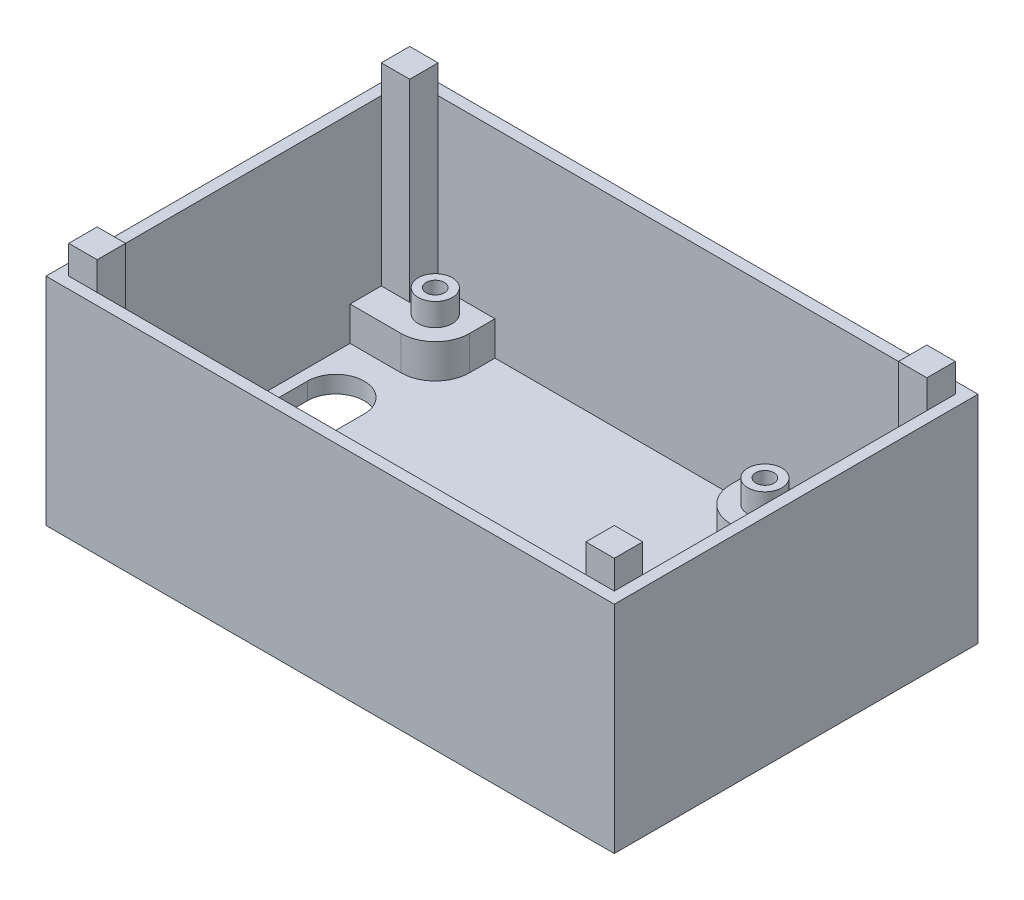
SolidWorks part; units mm, degrees
material "ABS"
ref_plane "Front Plane" through (0, 0, 0) normal (0, 0, 1) x (1, 0, 0)
ref_plane "Top Plane" through (0, 0, 0) normal (0, 1, 0) x (1, 0, 0)
ref_plane "Right Plane" through (0, 0, 0) normal (1, 0, 0) x (0, 0, -1)
sketch "Sketch1" plane through (0, 0, 0) normal (0, 1, 0) x (1, 0, 0)
  line L0 (-55, 0) -> (55, 0) construction
  line L1 (-50, 32) -> (50, 32)
  line L2 (-50, 32) -> (-50, -32)
  line L3 (-50, -32) -> (50, -32)
  line L4 (50, 32) -> (50, -32)
  line L5 (0, -55) -> (0, 55) construction
  dimension "D1" = 64
  dimension "D2" = 32
  dimension "D3" = 100
  dimension "D4" = 50
extrude "Boss-Extrude1" add sketch "Sketch1" along normal blind 3
sketch "Sketch2" plane through (0, 3, 0) normal (0, 1, 0) x (1, 0, 0)
  line L0 (50, 32) -> (-50, 32) construction
  line L1 (-48, -30) -> (48, -30)
  line L2 (-48, -30) -> (-48, 30)
  line L3 (-48, 30) -> (48, 30)
  line L4 (48, -30) -> (48, 30)
  line L5 (-48, -30) -> (48, 30) construction
  line L6 (-48, 30) -> (48, -30) construction
  line L7 (-50, 32) -> (-50, -32) construction
  line L9 (-50, 32) -> (50, 32)
  line L10 (-50, 32) -> (-50, -32)
  line L11 (-50, -32) -> (50, -32)
  line L12 (50, 32) -> (50, -32)
  point P0 (0, 0)
  dimension "D1" = 2
  dimension "D2" = 2
extrude "Boss-Extrude2" add sketch "Sketch2" along normal blind 35
sketch "Sketch6" plane through (0, 3, 0) normal (0, 1, 0) x (1, 0, 0)
  line L0 (-42.5, 30) -> (-42.5, -30) construction
  line L5 (-48, -30) -> (48, -30) construction
  line L6 (42.5, 30) -> (42.5, -30) construction
  line L7 (48, 30) -> (-48, 30) construction
  line L8 (-48, 30) -> (-48, -30) construction
  line L9 (48, -30) -> (48, 30) construction
  line L10 (-39, 28.5) -> (-39, -30) construction
  line L11 (-48, -23.5) -> (42.5, -23.5) construction
  line L12 (-48, 25.5) -> (42.5, 25.5) construction
  line L13 (-48, -30) -> (48, -30) construction
  line L14 (19, 27.1) -> (19, -30) construction
  line L16 (35.5962, 0) -> (7.276, 0) construction
  line L25 (-1.65, 0) -> (1.65, 0) construction
  circle A0 centre (-39, 25.5) radius 1.6
  circle A1 centre (19, 25.5) radius 1.6
  circle A2 centre (19, -23.5) radius 1.6
  circle A3 centre (-39, -23.5) radius 1.6
  circle A4 centre (-39, 25.5) radius 3
  circle A5 centre (19, 25.5) radius 3
  circle A6 centre (-39, -23.5) radius 3
  circle A7 centre (19, -23.5) radius 3
  dimension "D8" = 3.2
  dimension "D11" = 6
  dimension "D12" = 6
  dimension "D2" = 5.5
  dimension "D3" = 5.5
  dimension "D4" = 4.5
  dimension "D5" = 3.5
  dimension "D6" = 6.5
  dimension "D7" = 58
  dimension "D13" = 2
  dimension "D9" = 2
  dimension "D10" = 2
extrude "Boss-Extrude3" add sketch "Sketch6" along normal blind 10
sketch "Sketch7" plane through (0, 3, 0) normal (0, 1, 0) x (1, 0, 0)
  circle A0 centre (-39, 25.5) radius 1.5
  circle A1 centre (19, 25.5) radius 1.5
  circle A2 centre (19, -23.5) radius 1.5
  circle A3 centre (-39, -23.5) radius 1.5
  dimension "D3" = 3
  dimension "D1" = 2
  dimension "D2" = 2
extrude "Cut-Extrude2" cut sketch "Sketch7" against normal through all
sketch "Sketch10" plane through (0, 13, 0) normal (0, 1, 0) x (1, 0, 0)
  line L0 (-33, 25.5) -> (-33, 30)
  line L1 (48, 30) -> (-48, 30) construction
  line L2 (-39, 19.5) -> (-48, 19.5)
  line L3 (-48, 30) -> (-48, -30) construction
  line L4 (25, 25.5) -> (25, 30)
  line L5 (48, 30) -> (-48, 30) construction
  line L6 (13, 25.5) -> (13, 30)
  line L7 (25, -23.5) -> (25, -30)
  line L8 (-48, -30) -> (48, -30) construction
  line L9 (25, -30) -> (13, -30)
  line L10 (-48, -30) -> (48, -30) construction
  line L11 (13, -30) -> (13, -23.5)
  line L12 (25, 30) -> (13, 30)
  line L13 (-33, 30) -> (-48, 30)
  line L14 (-48, 30) -> (-48, 19.5)
  line L15 (-33, -23.5) -> (-33, -30)
  line L16 (-33, -30) -> (-48, -30)
  line L17 (-48, -30) -> (-48, -17.5)
  line L18 (-48, 30) -> (-48, -30) construction
  line L19 (-48, -17.5) -> (-39, -17.5)
  line L21 (48, 30) -> (38, 30)
  line L22 (48, 30) -> (48, 19.5)
  line L23 (48, 19.5) -> (38, 19.5)
  line L24 (38, 30) -> (38, 19.5)
  line L25 (48, -30) -> (38, -30)
  line L26 (48, -30) -> (48, -20)
  line L27 (48, -20) -> (38, -20)
  line L28 (38, -30) -> (38, -20)
  circle A0 centre (-39, 25.5) radius 3
  arc A1 (-39, 19.5) -> (-33, 25.5) centre (-39, 25.5) ccw
  arc A2 (13, 25.5) -> (25, 25.5) centre (19, 25.5) ccw
  circle A3 centre (19, 25.5) radius 3
  arc A4 (25, -23.5) -> (13, -23.5) centre (19, -23.5) ccw
  circle A5 centre (19, -23.5) radius 3
  arc A6 (-33, -23.5) -> (-39, -17.5) centre (-39, -23.5) ccw
  circle A7 centre (-39, -23.5) radius 3
  dimension "D3" = 6
  dimension "D4" = 10.5
  dimension "D5" = 10
  dimension "D6" = 10
  dimension "D7" = 10
  dimension "D1" = 2
  dimension "D2" = 2
extrude "Boss-Extrude8" add sketch "Sketch10" against normal blind 6 from offset 4 offset against normal yes
sketch "Sketch11" plane through (0, 0, 0) normal (0, -1, 0) x (1, 0, 0)
  line L0 (-41, -10) -> (-41, 10) construction
  line L1 (-46, -10) -> (-46, 10)
  line L2 (-36, -10) -> (-36, 10)
  line L3 (1.65, 0) -> (-1.65, 0) construction
  line L4 (-48, -19.5) -> (-48, 17.5) construction
  circle A0 centre (-39, 23.5) radius 3
  circle A1 centre (19, 23.5) radius 3
  circle A2 centre (19, -25.5) radius 3
  circle A3 centre (-39, -25.5) radius 3
  arc A4 (-46, -10) -> (-36, -10) centre (-41, -10) ccw
  arc A5 (-36, 10) -> (-46, 10) centre (-41, 10) ccw
  point P11 (-41, 0)
  dimension "D1" = 6
  dimension "D7" = 5
  dimension "D4" = 0
  dimension "D5" = 20
  dimension "D6" = 2
  dimension "D2" = 2
  dimension "D3" = 2
extrude "Cut-Extrude4" cut sketch "Sketch11" against normal blind 3
sketch "Sketch12" plane through (0, 38, 0) normal (0, 1, 0) x (1, 0, 0)
  line L1 (-48, 30) -> (-43, 30)
  line L2 (-48, 30) -> (-48, 25)
  line L3 (-48, 25) -> (-43, 25)
  line L4 (-43, 30) -> (-43, 25)
  line L5 (0, 43.3275) -> (0, 0) construction
  line L6 (0, 0) -> (63.2414, 0) construction
  line L7 (43, 30) -> (43, 25)
  line L8 (48, 25) -> (43, 25)
  line L9 (48, 30) -> (48, 25)
  line L10 (48, 30) -> (43, 30)
  line L11 (48, -30) -> (48, -25)
  line L12 (48, -25) -> (43, -25)
  line L13 (48, -30) -> (43, -30)
  line L14 (43, -30) -> (43, -25)
  line L15 (-43, -30) -> (-43, -25)
  line L16 (-48, -25) -> (-43, -25)
  line L17 (-48, -30) -> (-48, -25)
  line L18 (-48, -30) -> (-43, -30)
  dimension "D1" = 5
  dimension "D2" = 5
extrude "Boss-Extrude9" add sketch "Sketch12" along normal blind 5 and the other way blind 37
sketch "Sketch13" plane through (0, 0, 0) normal (0, -1, 0) x (1, 0, 0)
  line L0 (-55.9259, 0) -> (-25.6553, 0) construction
  line L2 (-48, 30) -> (-42.5, 30)
  line L3 (-48, 30) -> (-48, 24.5)
  line L4 (-48, 24.5) -> (-42.5, 24.5)
  line L5 (-42.5, 24.5) -> (-42.5, 30)
  line L9 (23.65, 0) -> (-23.65, 0) construction
  line L10 (-42.5, -30) -> (-42.5, -24.5)
  line L11 (-48, -24.5) -> (-42.5, -24.5)
  line L12 (-48, -24.5) -> (-48, -30)
  line L13 (-42.5, -30) -> (-48, -30)
  line L14 (0, 41.1614) -> (0, -44.4721) construction
  line L15 (0, -23.65) -> (0, 23.65) construction
  line L16 (42.5, -30) -> (42.5, -24.5)
  line L17 (42.5, -30) -> (48, -30)
  line L18 (48, -24.5) -> (48, -30)
  line L19 (48, -24.5) -> (42.5, -24.5)
  line L20 (42.5, 30) -> (42.5, 24.5)
  line L21 (48, 24.5) -> (42.5, 24.5)
  line L22 (48, 24.5) -> (48, 30)
  line L23 (42.5, 30) -> (48, 30)
  dimension "D1" = 5.5
  dimension "D2" = 5.5
  dimension "D3" = 5.5
  dimension "D4" = 5.5
  dimension "D5" = 5.5
extrude "Cut-Extrude5" cut sketch "Sketch13" against normal blind 7
fillet "Fillet1" radius 10 2 edges at (38, 6, 20) (38, 6, -19.5)
